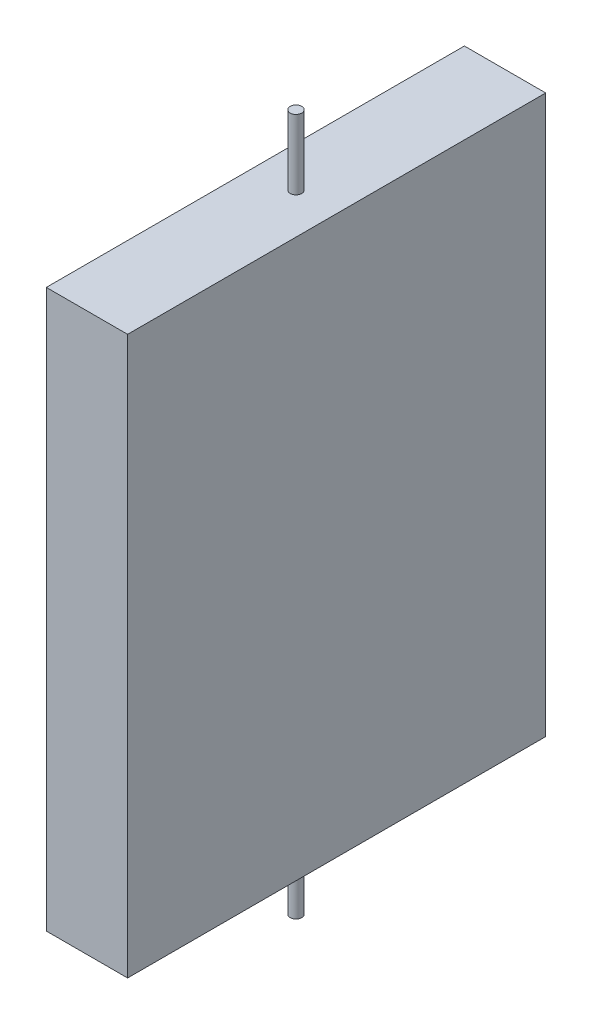
SolidWorks part; units mm, degrees
ref_plane "Front Plane" through (0, 0, 0) normal (1, 0, 0) x (0, 1, 0)
ref_plane "Top Plane" through (0, 0, 0) normal (0, 0, 1) x (0, 1, 0)
ref_plane "Right Plane" through (0, 0, 0) normal (0, 1, 0) x (-1, 0, 0)
sketch "Sketch1" plane through (0, 0, 0) normal (1, 0, 0) x (0, 1, 0)
  line L1 (-1200, 900) -> (1200, 900)
  line L2 (-1200, 900) -> (-1200, -900)
  line L3 (-1200, -900) -> (1200, -900)
  line L4 (1200, 900) -> (1200, -900)
  point P4 (0, 900)
  point P6 (1200, 0)
  dimension "D1" = 900
  dimension "D2" = 2400
  dimension "D3" = 1800
extrude "Boss-Extrude1" add sketch "Sketch1" along normal blind 175 and the other way blind 175 contours L2 L1 L4 L3
ref_plane "Plane1" through (0, 0, 0) normal (0, 1, 0) x (1, 0, 0)
sketch "Sketch2" plane through (0, 0, 0) normal (0, 1, 0) x (1, 0, 0)
  circle A0 centre (0, 0) radius 25
  dimension "D1" = 50
extrude "Boss-Extrude2" add sketch "Sketch2" along normal blind 1500 and the other way blind 1500
